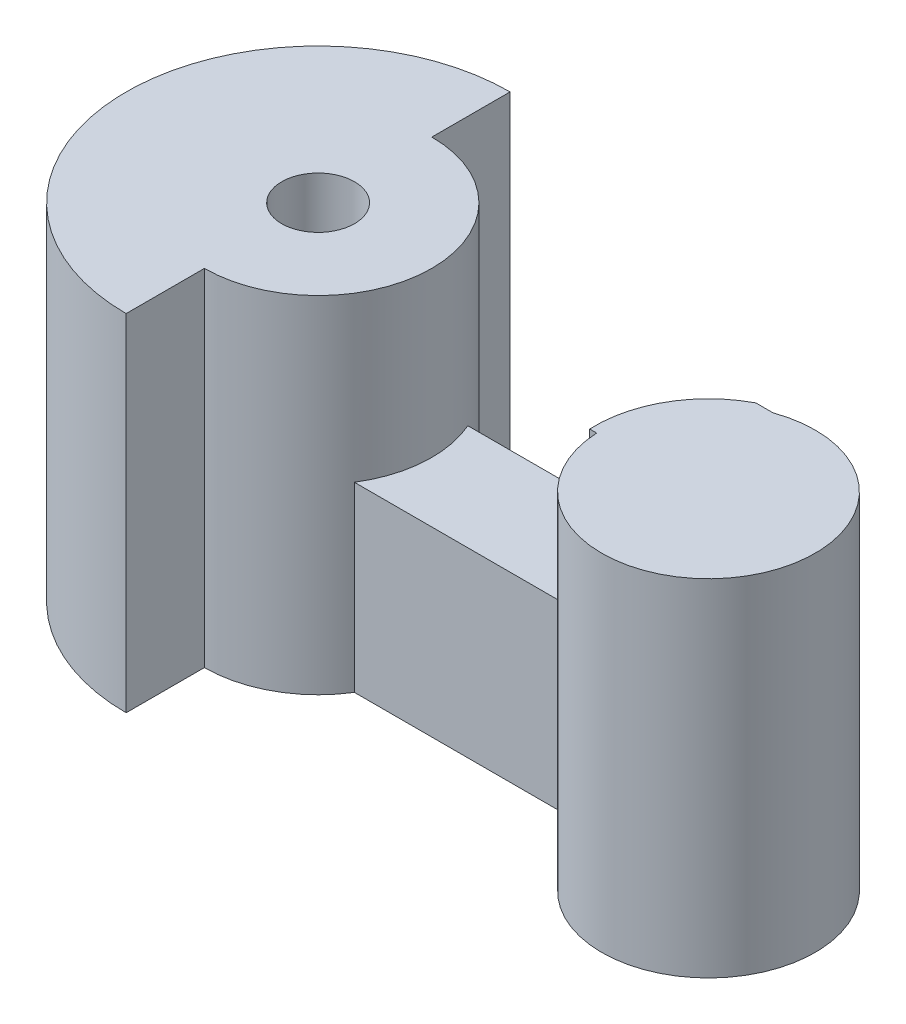
SolidWorks part; units mm, degrees
ref_plane "Front Plane" through (0, 0, 0) normal (0, 0, 1) x (1, 0, 0)
ref_plane "Top Plane" through (0, 0, 0) normal (0, 1, 0) x (1, 0, 0)
ref_plane "Right Plane" through (0, 0, 0) normal (1, 0, 0) x (0, 0, -1)
sketch "Sketch1" plane through (0, 0, 0) normal (0, 1, 0) x (1, 0, 0)
  line L0 (5.718, 4.5303) -> (5.718, 0.1867)
  line L6 (5.718, -1.8453) -> (5.718, -6.1889)
  line L8 (8.4119, -2.5095) -> (15.1747, -2.5095)
  line L9 (8.6279, 0.4407) -> (17.148, 0.4407)
  arc A0 (5.718, 4.5303) -> (5.718, -6.1889) centre (5.718, -0.8293) ccw
  arc A1 (15.1747, -2.5095) -> (17.148, 0.4407) centre (18.1512, -2.3654) ccw
  circle A2 centre (5.718, -0.8293) radius 3.175
  circle A3 centre (5.718, -0.8293) radius 1.016
  circle A4 centre (18.1512, -2.3654) radius 2.9801
extrude "Boss-Extrude3" add sketch "Sketch1" along normal blind 4.826 and the other way blind 4.826 contours A4 L9 A2 L8 | A1 A4 | A3 L6 A2 L0 | A3 L0 A2 L6 | A2 L0 A0 L6 region at (5.5981, 0, -3.438) region at (7.17, 0, 0.8293) region at (4.2659, 0, 0.8293) region at (12.2436, 0, 0.9807) region at (18.1512, 0, 2.3654)
sketch "Sketch4" plane through (0, 4.826, 0) normal (0, 1, 0) x (1, 0, 0)
  line L0 (8.4119, -2.5095) -> (15.1747, -2.5095)
  line L1 (8.6279, 0.4407) -> (17.148, 0.4407)
  circle A0 centre (18.1512, -2.3654) radius 3.175
  circle A1 centre (5.718, -0.8293) radius 3.175
  line M8 (8.4119, -2.5095) -> (15.1747, -2.5095)
  line M10 (17.148, 0.4407) -> (8.6279, 0.4407)
extrude "Cut-Extrude1" cut sketch "Sketch4" against normal blind 4.572 contours A1 A0 M8 M10 region at (12.118, 4.826, 0.9855)
